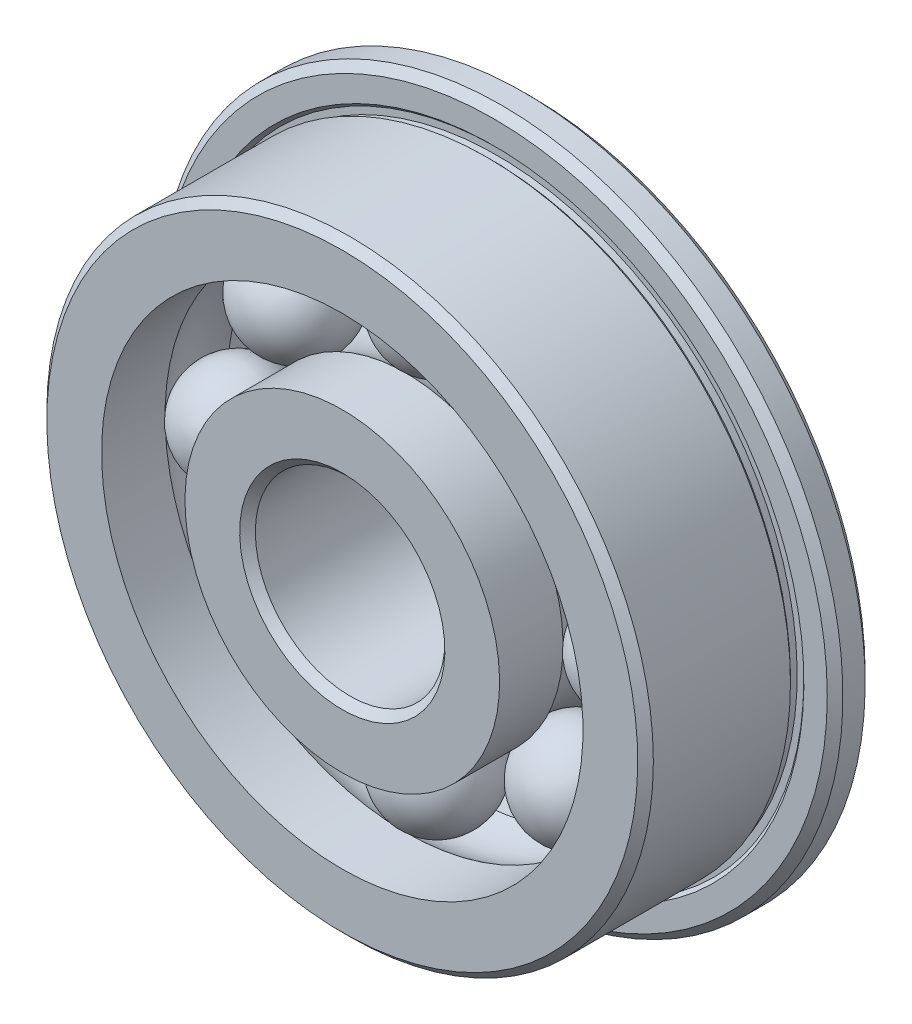
SolidWorks part; units mm, degrees
ref_plane "Front Plane" through (0, 0, 0) normal (0, 0, 1) x (1, 0, 0)
ref_plane "Top Plane" through (0, 0, 0) normal (0, 1, 0) x (1, 0, 0)
ref_plane "Right Plane" through (0, 0, 0) normal (1, 0, 0) x (0, 0, -1)
sketch "Sketch1" plane through (0, 0, 0) normal (1, 0, 0) x (0, 0, -1)
  line L0 (0, 8) -> (0, -8) construction
  line L1 (-2.5, 8) -> (2.5, 8) construction
  line L2 (0, 0) -> (2.5, 0) construction
  line L3 (2.5, 9) -> (2.5, -9) construction
  line L4 (2.5, -9) -> (1.5, -9) construction
  line L5 (2.5, 2.5) -> (0, 2.5) construction
  line L6 (2.5, 2.5) -> (2.5, -2.5) construction
  dimension "OD" = 16
  dimension "Width" = 5
  dimension "Flange Thickness" = 1
  dimension "ID" = 5
  dimension "Flange OD" = 18
sketch "Sketch2" plane through (0, 0, 0) normal (1, 0, 0) x (0, 0, -1)
  line L0 (2.5, 9) -> (1.5, 9)
  line L1 (1.5, 9) -> (1.5, 8.1768)
  line L2 (1.3232, 8) -> (-2.5, 8)
  line L3 (-2.5, 8) -> (-2.5, 6.35)
  line L4 (-2.5, 6.35) -> (-0.825, 6.35)
  line L5 (2.5, 9) -> (2.5, -9) construction
  line L6 (2.5, 6.35) -> (2.5, 9)
  line L7 (2.5, 2.5) -> (-2.5, 2.5)
  line L8 (-2.5, 2.5) -> (-2.5, 4.15)
  line L9 (-2.5, 4.15) -> (-0.825, 4.15)
  line L10 (2.5, 4.15) -> (2.5, 2.5)
  line L11 (0, 8) -> (0, 2.5) construction
  line L12 (-1.375, 5.25) -> (1.375, 5.25) construction
  line L13 (0.825, 6.35) -> (2.5, 6.35)
  line L14 (0.825, 4.15) -> (2.5, 4.15)
  line L15 (1.5, 8.1768) -> (1.5884, 8.0884)
  line L16 (1.5884, 8.0884) -> (1.5884, 7.9116)
  line L17 (1.5884, 7.9116) -> (1.4116, 7.9116)
  line L18 (1.4116, 7.9116) -> (1.3232, 8)
  line L19 (1.5, 8) -> (1.5884, 7.9116) construction
  line L20 (1.5884, 8.0884) -> (1.4116, 7.9116) construction
  line L21 (1.3232, 8) -> (1.5, 8) construction
  line L22 (1.5, 8) -> (1.5, 8.1768) construction
  circle A0 centre (0, 5.25) radius 1.375 construction
  arc A1 (-0.825, 6.35) -> (0.825, 6.35) centre (0, 5.25) cw
  arc A2 (-0.825, 4.15) -> (0.825, 4.15) centre (0, 5.25) ccw
  dimension "D1" = 5.5
  dimension "Ball Dia." = 2.75
  dimension "D2" = 135
  dimension "D3" = 0.25
  dimension "D4" = 2.2
  dimension "Race Thikness" = 1.65
revolve "Revolve1" add sketch "Sketch2" angle 360 about L2
fillet "Fillet1" radius 0.2062 3 edges at (0, -9, -2.5) (0, -9, -1.5) (0, -8, 2.5) profile chamfer
sketch "Sketch3" plane through (0, 0, 0) normal (0, 0, 1) x (1, 0, 0)
  line L0 (-2.5, 0) -> (2.5, 0) construction
  line L1 (-8, 0) -> (8, 0) construction
  point P5 (0, 0)
  dimension "ID2" = 5
  dimension "OD2" = 16
fillet "Fillet2" radius 0.2062 2 edges at (0, -2.5, -2.5) (0, -2.5, 2.5) profile chamfer
sketch "Sketch7" plane through (0, 0, 0) normal (0, 0, 1) x (1, 0, 0)
  line L0 (0, 6.625) -> (0, 3.875)
  line L1 (0, 9) -> (0, -9) construction
  line L2 (-1.7979, 6.625) -> (0, 0) construction
  line L3 (0, 0) -> (1.7979, 6.625) construction
  line L4 (1.7979, 6.625) -> (-1.7979, 6.625) construction
  circle A0 centre (0, 5.25) radius 1.375 construction
  circle A1 centre (0, 0) radius 6.625 construction
  circle A2 centre (0, 0) radius 3.875 construction
  arc A4 (0, 6.625) -> (0, 3.875) centre (0, 5.25) ccw
  dimension "D1" = 30.366
revolve "Revolve3" add sketch "Sketch7" angle 360 about L0
pattern_circular "CirPattern3" count 8 over 360 about axis through (0, 0, 0) along (0, 0, -1) of bodies 107
sketch "Sketch8" plane through (0, 0, 0) normal (1, 0, 0) x (0, 0, -1)
  line L0 (-2.5, 8) -> (2.5, 8) construction
  line L1 (2.5, 8) -> (2.5, 9) construction
  line L2 (-2.5, -8) -> (2.5, -8) construction
  line L3 (2.5, 9) -> (2.5, -9) construction
  dimension "D1" = 16
equation "\"Ball Dia.@Sketch2\" = ( \"OD@Sketch1\" - \"ID@Sketch1\" ) * .25"
equation "\"D3@Sketch2\"=\"Flange Thickness@Sketch1\"/4"
equation "\"D1@Fillet1\" = \"Race Thikness@Sketch2\" / 8"
equation "\"ID2@Sketch3\" = \"ID@Sketch1\""
equation "\"OD2@Sketch3\" = \"OD@Sketch1\""
equation "\"D1@Fillet2\" = \"Race Thikness@Sketch2\" / 8"
equation "\"D1@CirPattern3\"=360/\"D1@Sketch7\"-4"
equation "\"D4@Sketch2\" = ( \"OD@Sketch1\" - \"ID@Sketch1\" ) * .2"
